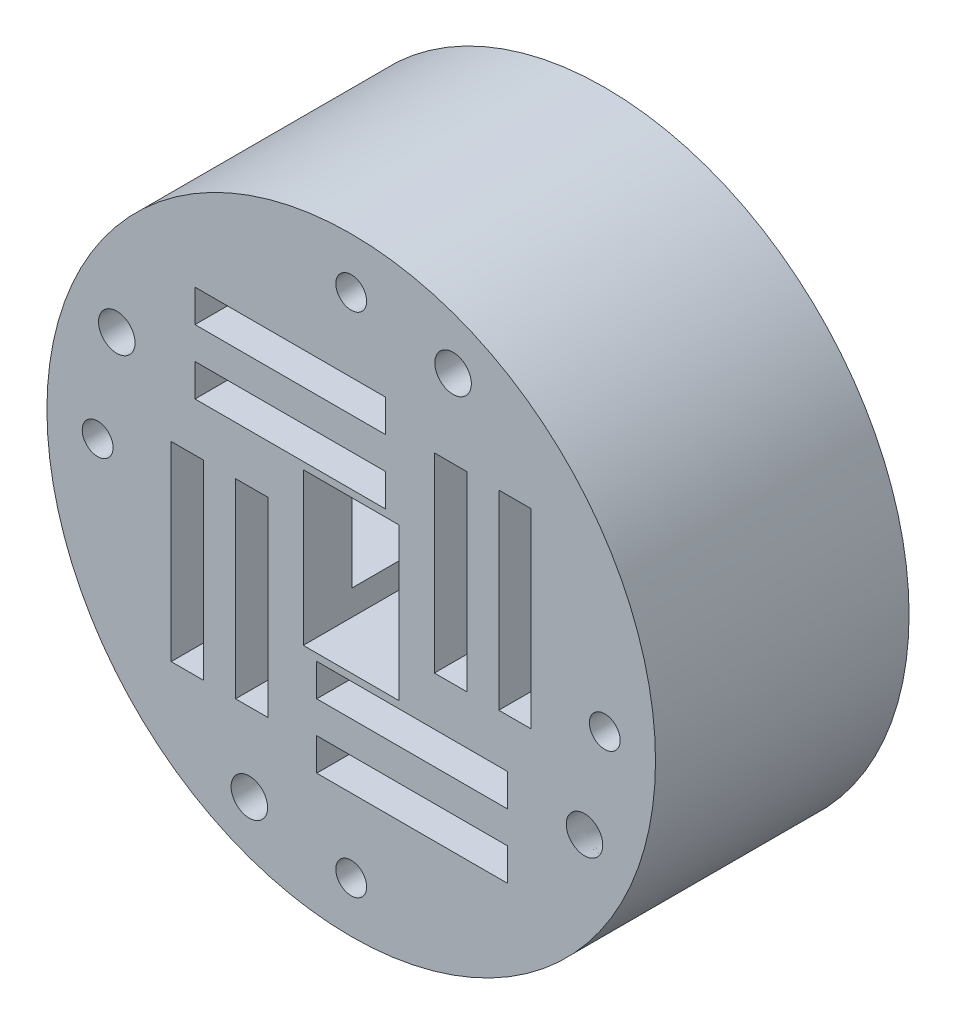
SolidWorks part; units mm, degrees
material "ABS"
ref_plane "Front Plane" through (0, 0, 0) normal (0, 0, 1) x (1, 0, 0)
ref_plane "Top Plane" through (0, 0, 0) normal (0, 1, 0) x (1, 0, 0)
ref_plane "Right Plane" through (0, 0, 0) normal (1, 0, 0) x (0, 0, -1)
sketch "Sketch1" plane through (0, 0, 0) normal (0, 0, 1) x (1, 0, 0)
  circle A0 centre (0, 0) radius 34.29
  circle A1 centre (0, 0) radius 38.1
  dimension "D1" = 76.2
  dimension "D2" = 3.81
extrude "Boss-Extrude1" add sketch "Sketch1" along normal blind 31.75
sketch "Sketch2" plane through (0, 0, 31.75) normal (0, 0, 1) x (1, 0, 0)
  circle A0 centre (0, 0) radius 38.1
  dimension "D1" = 76.2
extrude "Boss-Extrude2" add sketch "Sketch2" against normal blind 21.336
sketch "Sketch3" plane through (0, 0, 31.75) normal (0, 0, 1) x (1, 0, 0)
  line L1 (-6, -9.525) -> (6, -9.525)
  line L2 (-6, -9.525) -> (-6, 9.525)
  line L3 (-6, 9.525) -> (6, 9.525)
  line L4 (6, -9.525) -> (6, 9.525)
  line L5 (-6, -9.525) -> (6, 9.525) construction
  line L6 (-6, 9.525) -> (6, -9.525) construction
  point P0 (0, 0)
  dimension "D1" = 12
  dimension "D2" = 19.05
extrude "Cut-Extrude1" cut sketch "Sketch3" against normal up to surface (21.336 mm away) up to face at (34.29, 0, 10.414)
sketch "Sketch4" plane through (0, 0, 31.75) normal (0, 0, 1) x (1, 0, 0)
  line L1 (10.414, 19.558) -> (14.478, 19.558)
  line L2 (10.414, 19.558) -> (10.414, -4.318)
  line L3 (10.414, -4.318) -> (14.478, -4.318)
  line L4 (14.478, 19.558) -> (14.478, -4.318)
  line L5 (18.478, 19.558) -> (22.542, 19.558)
  line L6 (18.478, 19.558) -> (18.478, -4.318)
  line L7 (18.478, -4.318) -> (22.542, -4.318)
  line L8 (22.542, 19.558) -> (22.542, -4.318)
  line L56 (19.558, -10.414) -> (-4.318, -10.414)
  line L57 (19.558, -10.414) -> (19.558, -14.478)
  line L58 (19.558, -14.478) -> (-4.318, -14.478)
  line L59 (-4.318, -10.414) -> (-4.318, -14.478)
  line L60 (19.558, -18.478) -> (-4.318, -18.478)
  line L61 (19.558, -18.478) -> (19.558, -22.542)
  line L62 (19.558, -22.542) -> (-4.318, -22.542)
  line L63 (-4.318, -18.478) -> (-4.318, -22.542)
  line L64 (-10.414, -19.558) -> (-10.414, 4.318)
  line L65 (-10.414, -19.558) -> (-14.478, -19.558)
  line L66 (-14.478, -19.558) -> (-14.478, 4.318)
  line L67 (-10.414, 4.318) -> (-14.478, 4.318)
  line L68 (-18.478, -19.558) -> (-18.478, 4.318)
  line L69 (-18.478, -19.558) -> (-22.542, -19.558)
  line L70 (-22.542, -19.558) -> (-22.542, 4.318)
  line L71 (-18.478, 4.318) -> (-22.542, 4.318)
  line L72 (-19.558, 10.414) -> (4.318, 10.414)
  line L73 (-19.558, 10.414) -> (-19.558, 14.478)
  line L74 (-19.558, 14.478) -> (4.318, 14.478)
  line L75 (4.318, 10.414) -> (4.318, 14.478)
  line L76 (-19.558, 18.478) -> (4.318, 18.478)
  line L77 (-19.558, 18.478) -> (-19.558, 22.542)
  line L78 (-19.558, 22.542) -> (4.318, 22.542)
  line L79 (4.318, 18.478) -> (4.318, 22.542)
  point P36 (0, 0)
  point P37 (0, 0)
  dimension "D6" = 4
  dimension "D1" = 4.064
  dimension "D2" = 4
  dimension "D3" = 23.876
  dimension "D4" = 4.318
  dimension "D5" = 14.478
extrude "Cut-Extrude2" cut sketch "Sketch4" against normal blind 7.62
sketch "Sketch5" plane through (0, 0, 10.414) normal (0, 0, -1) x (-1, 0, 0)
  line L1 (-12.7, -6.35) -> (31.75, -6.35)
  line L2 (-12.7, -6.35) -> (-12.7, 6.35)
  line L3 (-12.7, 6.35) -> (31.75, 6.35)
  line L4 (31.75, -6.35) -> (31.75, 6.35)
  point P0 (0, 0)
  dimension "D1" = 12.7
  dimension "D2" = 31.75
  dimension "D3" = 6.35
  dimension "D4" = 12.7
extrude "Cut-Extrude3" cut sketch "Sketch5" against normal blind 15.24
sketch "Sketch6" plane through (0, 0, 10.414) normal (0, 0, -1) x (-1, 0, 0)
  line L0 (2.1029, 22.81) -> (25.6029, 22.81)
  line L1 (25.6029, 22.81) -> (25.6029, 9.96)
  line L2 (25.6029, 9.96) -> (28.6029, 9.96)
  line L3 (28.6029, 9.96) -> (28.6029, 8.96)
  line L4 (28.6029, 8.96) -> (25.6029, 8.96)
  line L5 (25.6029, 8.96) -> (25.6029, 6.35)
  line L6 (31.75, 6.35) -> (6, 6.35) construction
  line L7 (25.6029, 6.35) -> (31.75, 6.35)
  line L8 (31.75, 6.35) -> (31.75, -6.35)
  line L9 (31.75, -6.35) -> (-12.7, -6.35)
  line L10 (-12.7, -6.35) -> (-12.7, 6.35)
  line L11 (-12.7, 6.35) -> (2.1029, 6.35)
  line L12 (2.1029, 6.35) -> (2.1029, 8.96)
  line L13 (2.1029, 8.96) -> (-0.8971, 8.96)
  line L14 (-0.8971, 8.96) -> (-0.8971, 9.96)
  line L15 (-0.8971, 9.96) -> (2.1029, 9.96)
  line L16 (2.1029, 9.96) -> (2.1029, 22.81)
  line L17 (2.1029, 6.35) -> (2.1029, 3.81) construction
  line L18 (2.1029, 3.81) -> (25.6029, 3.81) construction
  line L19 (25.6029, 3.81) -> (25.6029, 6.35) construction
  circle A2 centre (0, 0) radius 38.1
  circle A3 centre (0, 0) radius 38.1 construction
  circle A4 centre (0, 0) radius 34.29 construction
  dimension "D1" = 19
  dimension "D2" = 23.5
  dimension "D3" = 29.5
  dimension "D4" = 5.15
  dimension "D5" = 2.54
  dimension "D6" = 1
extrude "Boss-Extrude3" add sketch "Sketch6" along normal blind 8
sketch "Sketch7" plane through (0, 0, 10.414) normal (0, 0, 1) x (1, 0, 0)
  line L1 (-6, -9.525) -> (6, -9.525)
  line L2 (-6, -9.525) -> (-6, 9.525)
  line L3 (-6, 9.525) -> (6, 9.525)
  line L4 (6, -9.525) -> (6, 9.525)
extrude "Boss-Extrude4" add sketch "Sketch7" along normal blind 2.54
sketch "Sketch8" plane through (0, 0, 2.414) normal (0, 0, -1) x (-1, 0, 0)
  line L1 (28.6029, 9.96) -> (25.6029, 9.96) construction
  circle A0 centre (29.3529, 12.754) radius 2.286
  circle A1 centre (0, 0) radius 34.29 construction
  circle A5 centre (12.754, -29.3529) radius 2.286
  circle A7 centre (-12.754, 29.3529) radius 2.286
  circle A8 centre (-29.3529, -12.754) radius 2.286 [skipped]
  point P15 (0, 0)
  dimension "D1" = 4.572
  dimension "D2" = 2.794
  dimension "D3" = 4
extrude "Cut-Extrude4" cut sketch "Sketch8" against normal through all
chamfer "Chamfer1" distance 1.905 angle 45 1 edges at (34.29, 0, 0)
sketch "Sketch9" plane through (0, 0, 2.414) normal (0, 0, -1) x (-1, 0, 0)
  circle A0 centre (0, -31.75) radius 1.9304
  circle A1 centre (-31.75, 0) radius 1.9304
  circle A2 centre (0, 31.75) radius 1.9304
  circle A3 centre (31.75, 0) radius 1.9304
  point P9 (0, 0)
  dimension "D1" = 3.8608
  dimension "D2" = 31.75
  dimension "D3" = 4
extrude "Cut-Extrude5" cut sketch "Sketch9" against normal through all
sketch "Sketch10" plane through (0, 0, 31.75) normal (0, 0, 1) x (1, 0, 0)
  line L0 (-4.318, -14.478) -> (19.558, -14.478) construction
  circle A0 centre (29.21, -12.446) radius 2.286
  dimension "D3" = 4.572
  dimension "D1" = 2.032
  dimension "D2" = 9.652
sketch3d "3DSketch1"
  spline S1 degree 3 poles (29.21, -12.446, 31.75) (28.042, -13.6065, 25.0786) (25.3651, -15.5316, 21.1462) (18.6134, -22.0102, 16.5039) (14.8693, -23.1531, 15.3723) (10.0157, -25.2815, 10.4751) (8.0896, -27.4395, 0) knots 0 0 0 0 0.447008 0.522827 0.758186 1 1 1 1
sweep "Cut-Sweep1" cut profiles "Sketch10" path "3DSketch1"
sketch "Sketch14" plane through (0, 0, 2.414) normal (0, 0, -1) x (-1, 0, 0)
  line L1 (-27.94, -15.113) -> (-20.32, -15.113)
  line L2 (-27.94, -15.113) -> (-27.94, 15.113)
  line L3 (-27.94, 15.113) -> (-20.32, 15.113)
  line L4 (-20.32, -15.113) -> (-20.32, 15.113)
  line L5 (-27.94, -15.113) -> (-20.32, 15.113) construction
  line L6 (-27.94, 15.113) -> (-20.32, -15.113) construction
  circle A0 centre (-31.75, 0) radius 1.9304 construction
  point P0 (-24.13, 0)
  dimension "D3" = 3.81
  dimension "D1" = 7.62
  dimension "D2" = 30.226
extrude "Cut-Extrude6" cut sketch "Sketch14" against normal blind 8.89
